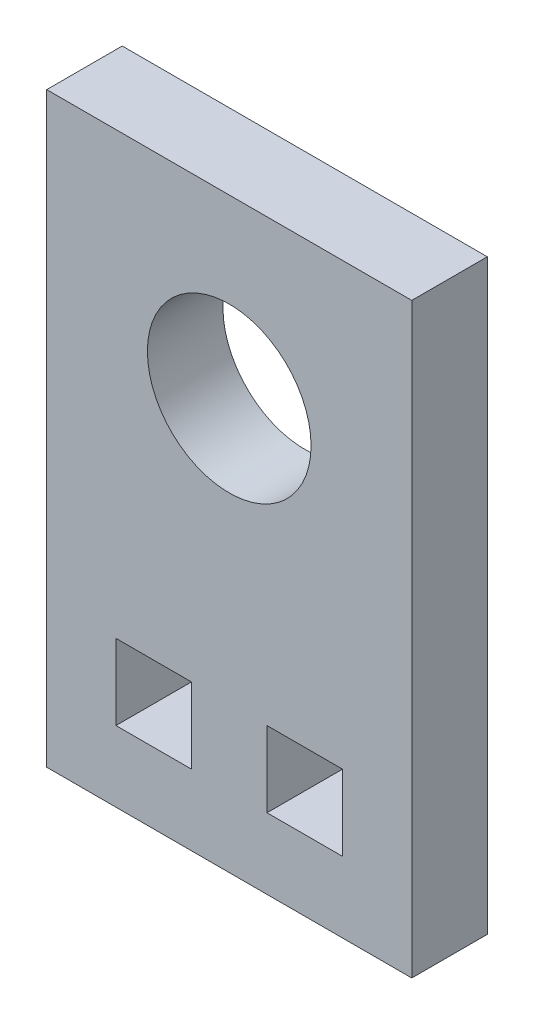
SolidWorks part; units mm, degrees
ref_plane "Front Plane" through (0, 0, 0) normal (0, 0, 1) x (1, 0, 0)
ref_plane "Top Plane" through (0, 0, 0) normal (0, 1, 0) x (1, 0, 0)
ref_plane "Right Plane" through (0, 0, 0) normal (1, 0, 0) x (0, 0, -1)
sketch "Sketch1" plane through (0, 0, 0) normal (0, 0, 1) x (1, 0, 0)
  line L0 (0.0436, 13.3694) -> (0.0436, -7.1259) construction
  line L1 (-7.2064, -7.1306) -> (-7.2064, 13.3694)
  line L2 (-7.2064, 13.3694) -> (7.2936, 13.3694)
  line L3 (7.2936, -6.9397) -> (7.2936, 13.3694)
  line L4 (-7.2064, -7.1306) -> (7.2936, 13.3694) construction
  line L5 (-7.2064, 13.3694) -> (7.2936, -6.9397) construction
  line L6 (-4.4564, -7.1306) -> (-4.4564, -4.1306)
  line L7 (-4.4564, -4.1306) -> (-1.4564, -4.1306)
  line L8 (-1.4564, -7.1306) -> (-1.4564, -4.1306)
  line L9 (4.5436, -4.1306) -> (1.5436, -4.1306)
  line L10 (1.5436, -7.1306) -> (1.5436, -4.1306)
  line L11 (4.5436, -7.1306) -> (4.5436, -4.1306)
  line L12 (1.5436, -7.1306) -> (4.5436, -7.1306)
  line L13 (-4.4564, -7.1306) -> (-1.4564, -7.1306)
  line L14 (-7.2064, -7.1306) -> (-7.2064, -9.9397)
  line L15 (-7.2064, -9.9397) -> (7.2936, -9.9397)
  line L16 (7.2936, -6.9397) -> (7.2936, -9.9397)
  circle A0 centre (0.0436, 6.3694) radius 3.25
  point P0 (0.0775, 3.1674)
  dimension "D10" = 6.5
  dimension "D1" = 20.5
  dimension "D2" = 3
  dimension "D3" = 3
  dimension "D4" = 1.5
  dimension "D5" = 3
  dimension "D6" = 3
  dimension "D7" = 14.5
  dimension "D8" = 0
  dimension "D9" = 7
extrude "Boss-Extrude1" add sketch "Sketch1" along normal blind 3
